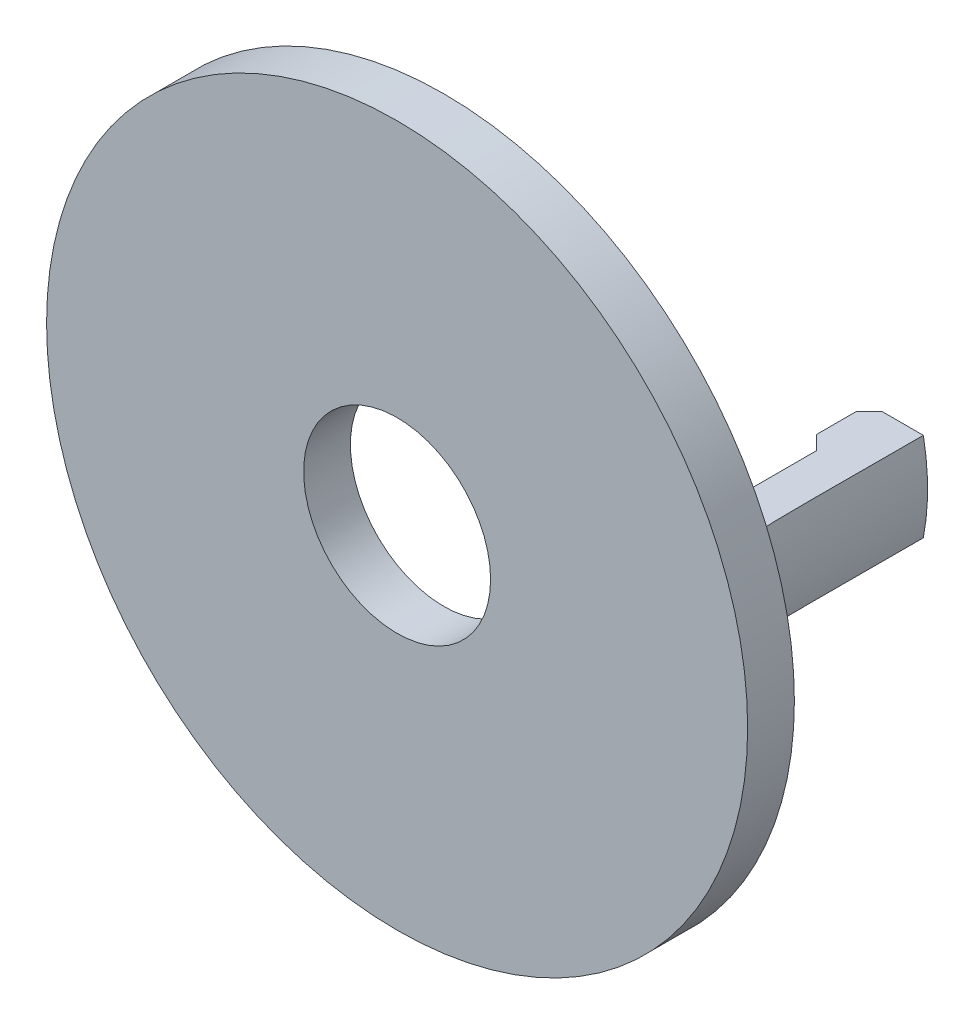
SolidWorks part; units mm, degrees
ref_plane "Front" through (0, 0, 0) normal (0, 0, 1) x (1, 0, 0)
ref_plane "Top" through (0, 0, 0) normal (0, 1, 0) x (1, 0, 0)
ref_plane "Right" through (0, 0, 0) normal (1, 0, 0) x (0, 0, -1)
sketch "Sketch1" plane through (0, 0, 0) normal (0, 0, 1) x (1, 0, 0)
  circle A0 centre (0, 0) radius 26.5
  circle A1 centre (0, 0) radius 37.5
  circle A2 centre (-2, 0) radius 26.5
  dimension "D1" = 53
  dimension "D2" = 75
  dimension "D3" = 2
sketch "Sketch4" plane through (0, 0, 0) normal (0, 0, 1) x (1, 0, 0)
  circle A0 centre (0, 0) radius 37.5
  dimension "D1" = 75
extrude "Boss-Extrude2" add sketch "Sketch4" along normal blind 5
sketch "Sketch5" plane through (0, 0, 5) normal (0, 0, 1) x (1, 0, 0)
  circle A0 centre (0, 0) radius 10
  dimension "D1" = 20
extrude "Cut-Extrude1" cut sketch "Sketch5" against normal through all
sketch "Sketch6" plane through (0, 0, 0) normal (0, 1, 0) x (1, 0, 0)
  line L0 (20, 0) -> (26.5, 0) construction
  line L1 (26.5, 0) -> (26.5, 27) construction
  line L2 (17.3536, 0) -> (26.5, 0)
  line L3 (26.5, 27) -> (20, 27) construction
  line L4 (20, 27) -> (18.5, 25.5) construction
  line L5 (18.5, 21) -> (20, 19.5) construction
  line L6 (20, 19.5) -> (20, 0) construction
  line L7 (20.25, 19.6036) -> (20.25, 2.8964)
  line L8 (20, 3) -> (17, 0) construction
  line L9 (20.25, 19.6036) -> (18.75, 21.1036)
  line L10 (18.5, 25.5) -> (18.5, 21) construction
  line L11 (18.75, 21.1036) -> (18.75, 25.3964)
  line L12 (26.5, 0) -> (26.5, 26.75)
  line L13 (17, 0) -> (20, 0) construction
  line L14 (20.25, 2.8964) -> (17.3536, 0)
  line L15 (18.75, 25.3964) -> (20.1036, 26.75)
  line L16 (20.1036, 26.75) -> (26.5, 26.75)
  line L17 (25, 26.5113) -> (25, 41.0721) construction
  line L18 (25, 12.4795) -> (25, 18.7128) construction
  spline S0 degree 3 poles (25, 26.75) (25, 22.7282) (24.9901, 20.5425) (25.0119, 14.9424) (24.7749, 4.9839) (26.5, 0) knots 0 0 0 0 0.446605 0.546605 1 1 1 1
  dimension "D1" = 135
  dimension "D2" = 6.5
  dimension "D3" = 8
  dimension "D4" = 27
  dimension "D5" = 7.5
  dimension "D6" = 0.25
  dimension "D7" = 0.25
  dimension "D8" = 0.25
  dimension "D9" = 0.25
  dimension "D10" = 3
  dimension "D11" = 3
  dimension "D12" = 0.25
  dimension "D13" = 1.5
  dimension "D14" = 0.25
extrude "Boss-Extrude3" add sketch "Sketch6" along normal blind 4.75 and the other way blind 4.75 contours L16 L15 L11 L9 L7 L14 L2 | L12 L16 region at (22.4479, 0, -13.2155) region at (25.7982, 0, -14.9997)
extrude "Cut-Extrude2" cut sketch "Sketch1" against normal through all contours A1 A2 A0 region at (-36.4393, 0, 0)
ref_axis "Axis1" through (0, 0, 0) along (0, 0, -1)
revolve "Cut-Revolve1" cut sketch "Sketch6<4>" angle 360 about axis through (0, 0, 0) along (0, 0, -1) region at (25.7982, 0, -14.9997)
sketch "Sketch6<4>" plane through (0, 0, 0) normal (0, 1, 0) x (1, 0, 0) same geometry as "Sketch6"
mirror "Mirror1" about plane through (0, 0, 0) normal (1, 0, 0) of "Boss-Extrude3", "Cut-Extrude2", "Cut-Revolve1"
equation "\"female_make_room\"= 0.25"
equation "\"D6@Sketch6\"=\"female_make_room\""
equation "\"D8@Sketch6\"=\"female_make_room\""
equation "\"D7@Sketch6\"=\"female_make_room\""
equation "\"D9@Sketch6\"=\"female_make_room\""
equation "\"D12@Sketch6\"=\"female_make_room\""
equation "\"D14@Sketch6\"=\"female_make_room\""
